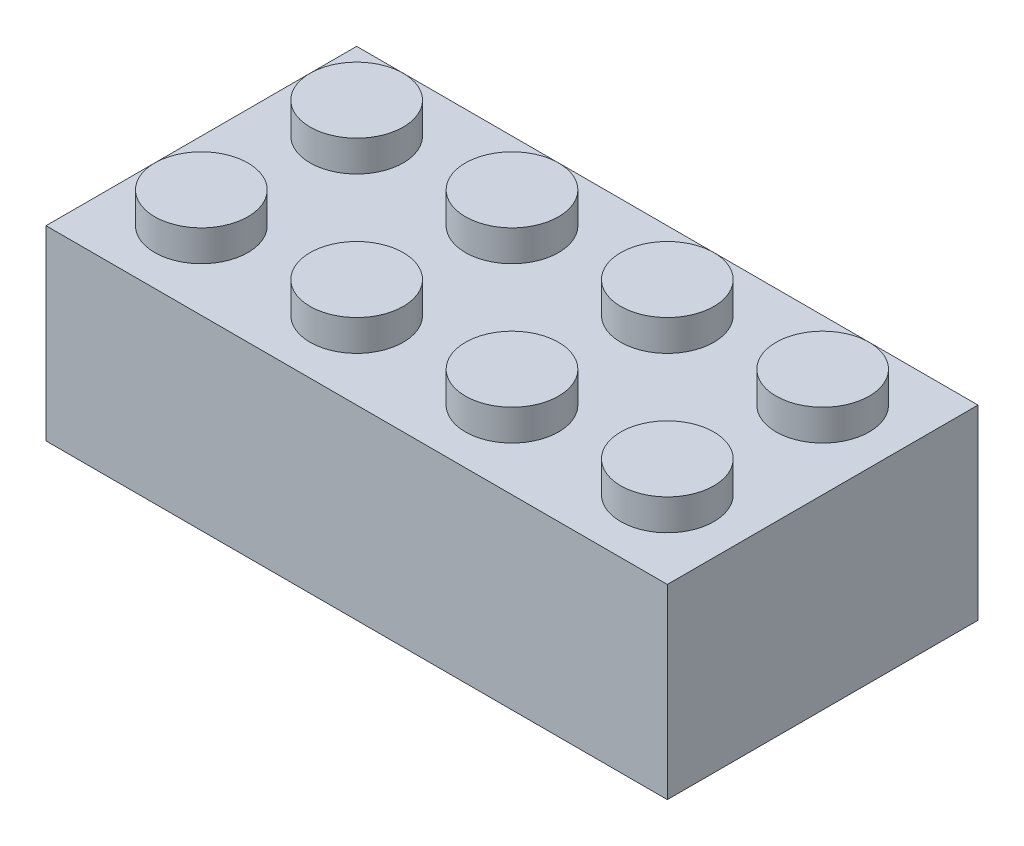
SolidWorks part; units mm, degrees
ref_plane "Front Plane" through (0, 0, 0) normal (0, 0, 1) x (1, 0, 0)
ref_plane "Top Plane" through (0, 0, 0) normal (0, 1, 0) x (1, 0, 0)
ref_plane "Right Plane" through (0, 0, 0) normal (1, 0, 0) x (0, 0, -1)
sketch "Sketch1" plane through (0, 0, 0) normal (0, 1, 0) x (1, 0, 0)
  line L1 (-10, -5) -> (10, -5)
  line L2 (-10, -5) -> (-10, 5)
  line L3 (-10, 5) -> (10, 5)
  line L4 (10, -5) -> (10, 5)
  line L5 (-10, -5) -> (10, 5) construction
  line L6 (-10, 5) -> (10, -5) construction
  line L7 (-9, -4) -> (9, -4)
  line L8 (-9, -4) -> (-9, 4)
  line L9 (-9, 4) -> (9, 4)
  line L10 (9, -4) -> (9, 4)
  line L11 (-9, -4) -> (9, 4) construction
  line L12 (-9, 4) -> (9, -4) construction
  circle A0 centre (-2.5, 2.5) radius 1.5
  circle A1 centre (-7.5, 2.5) radius 1.5
  circle A2 centre (2.5, 2.5) radius 1.5
  circle A3 centre (7.5, 2.5) radius 1.5
  circle A4 centre (-2.5, -2.5) radius 1.5
  circle A5 centre (2.5, -2.5) radius 1.5
  circle A6 centre (7.5, -2.5) radius 1.5
  circle A7 centre (-7.5, -2.5) radius 1.5
  circle A8 centre (-5, 0) radius 2.0355
  circle A9 centre (-5, 0) radius 1.5
  circle A10 centre (0, 0) radius 1.5
  circle A11 centre (0, 0) radius 2.0355
  circle A12 centre (5, 0) radius 1.5
  circle A13 centre (5, 0) radius 2.0355
  circle A14 centre (-7.5, 2.5) radius 0.75
  circle A15 centre (-2.5, 2.5) radius 0.75
  circle A16 centre (2.5, 2.5) radius 0.75
  circle A17 centre (7.5, 2.5) radius 0.75
  circle A18 centre (-2.5, -2.5) radius 0.75
  circle A19 centre (2.5, -2.5) radius 0.75
  circle A20 centre (7.5, -2.5) radius 0.75
  circle A21 centre (-7.5, -2.5) radius 0.75
  point P0 (0, 0)
  point P9 (0, 0)
  dimension "D5" = 1
  dimension "D7" = 4
  dimension "D9" = 3
  dimension "D11" = 1.5
  dimension "D1" = 10
  dimension "D2" = 20
  dimension "D3" = 2.5
  dimension "D4" = 2.5
  dimension "D6" = 1
  dimension "D8" = 2
  dimension "D10" = 3
  dimension "D12" = 4
  dimension "D13" = 2
extrude "Boss-Extrude1" add sketch "Sketch1" along normal blind 2 contours A1 | A0 | A2 | A3 | A6 | A5 | A4 | A7 | A14 | A15 | A16 | A17 | A20 | A19 | A18 | A21 region at (-8.5307, 0, 3.5307) region at (-3.8466, 0, 3.0578) region at (-8.5307, 0, -3.5307) region at (1.1534, 0, 3.0578) region at (6.1534, 0, 3.0578) region at (-1.4693, 0, -3.5307) region at (3.5307, 0, -3.5307) region at (8.0578, 0, -1.1534) region at (-7.5, 0, -2.5) region at (-2.5, 0, -2.5) region at (2.5, 0, -2.5) region at (7.5, 0, -2.5) region at (-2.5, 0, 2.5) region at (2.5, 0, 2.5) region at (7.5, 0, 2.5) region at (-7.5, 0, 2.5)
extrude "Boss-Extrude2" add sketch "Sketch1<3>" along normal blind 1 contours L2 L3 L4 L1
sketch "Sketch1<3>" plane through (0, 0, 0) normal (0, 1, 0) x (1, 0, 0) same geometry as "Sketch1"
extrude "Cut-Extrude1" cut sketch "Sketch1<4>" along normal blind 1 contours A21 | A18 | A19 | A20 | A17 | A16 | A15 | A14 region at (-7.5, 0, -2.5) region at (-2.5, 0, -2.5) region at (2.5, 0, -2.5) region at (7.5, 0, -2.5) region at (-2.5, 0, 2.5) region at (2.5, 0, 2.5) region at (7.5, 0, 2.5) region at (-7.5, 0, 2.5)
sketch "Sketch1<4>" plane through (0, 0, 0) normal (0, 1, 0) x (1, 0, 0) same geometry as "Sketch1"
extrude "Boss-Extrude3" add sketch "Sketch1<5>" against normal blind 5 contours L1 L4 L3 L2 L10 L7 L8 L9 | A8 A9 | A11 A10 | A13 A12 region at (-9.7764, 0, 0) region at (-6.978, 0, 0) region at (0, 0, 1.978) region at (5, 0, 1.978)
sketch "Sketch1<5>" plane through (0, 0, 0) normal (0, 1, 0) x (1, 0, 0) same geometry as "Sketch1"
